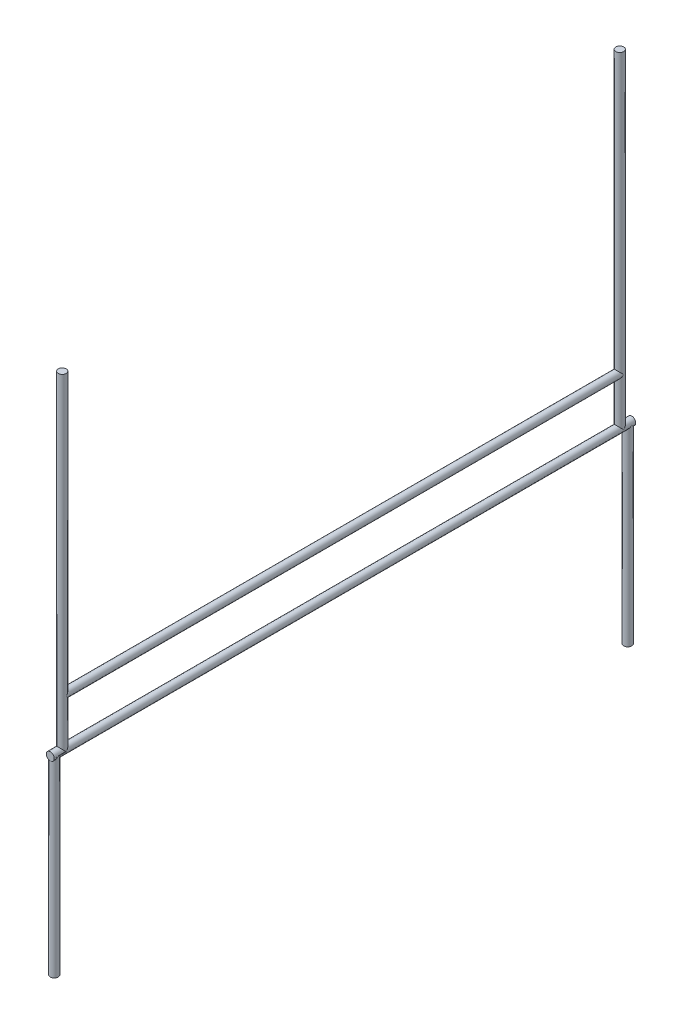
SolidWorks part; units mm, degrees
ref_plane "Front Plane" through (0, 0, 0) normal (0, 0, 1) x (1, 0, 0)
ref_plane "Top Plane" through (0, 0, 0) normal (0, 1, 0) x (1, 0, 0)
ref_plane "Right Plane" through (0, 0, 0) normal (1, 0, 0) x (0, 0, -1)
sketch "Sketch1" plane through (0, 0, 0) normal (0, 1, 0) x (1, 0, 0)
  line L0 (0, 0) -> (0, -7315.2) construction
  circle A0 centre (0, 0) radius 50.8
  circle A1 centre (0, -7315.2) radius 50.8
  dimension "D1" = 101.6
  dimension "D2" = 7315.2
extrude "Boss-Extrude1" add sketch "Sketch1" along normal blind 2438.4
ref_plane "Plane3" through (0, 0, -50.8) normal (0, 0, -1) x (-1, 0, 0)
ref_plane "Plane1" through (0, 2438.4, 0) normal (0, 1, 0) x (1, 0, 0)
sketch "Sketch3" plane through (0, 2438.4, 0) normal (0, 1, 0) x (1, 0, 0)
  line L0 (0, 0) -> (0, -7315.2)
  line L1 (0, 0) -> (0, 50.8)
  line L2 (0, -7315.2) -> (0, -7366)
  circle A2 centre (0, -7315.2) radius 50.8 construction
  circle A3 centre (0, 0) radius 50.8 construction
  circle A4 centre (0, -7315.2) radius 50.8 construction
sketch "Sketch4" plane through (0, 0, -50.8) normal (0, 0, -1) x (-1, 0, 0)
  circle A0 centre (0, 2438.4) radius 50.8
  dimension "D1" = 101.6
sweep "Sweep1" add profiles "Sketch4" path "Sketch3"
sketch "Sketch6" plane through (0, 2438.4, 0) normal (0, 1, 0) x (1, 0, 0)
  line L0 (0, -101.6) -> (0, 50.8) construction
  line L1 (55.88, 50.8) -> (-55.88, 50.8) construction
  line L2 (0, -7213.6) -> (0, -7366) construction
  line L3 (-50.8, -7366) -> (50.8, -7366) construction
  circle A0 centre (0, -101.6) radius 50.8
  circle A1 centre (0, -7213.6) radius 50.8
  dimension "D1" = 101.6
  dimension "D2" = 7112
extrude "Boss-Extrude2" add sketch "Sketch6" along normal blind 4178.3
ref_plane "Plane4" through (0, 0, 152.4) normal (0, 0, 1) x (1, 0, 0)
sketch "Sketch7" plane through (0, 0, 152.4) normal (0, 0, 1) x (1, 0, 0)
  line L0 (0, 3048) -> (0, 0) construction
  circle A0 centre (0, 3048) radius 50.8
  dimension "D1" = 101.6
  dimension "D2" = 3048
extrude "Boss-Extrude4" add sketch "Sketch7" along normal up to surface and the other way up to surface up to face at (0, 2489.2, 7213.6) other way up to face at (0, 2489.2, 101.6)
